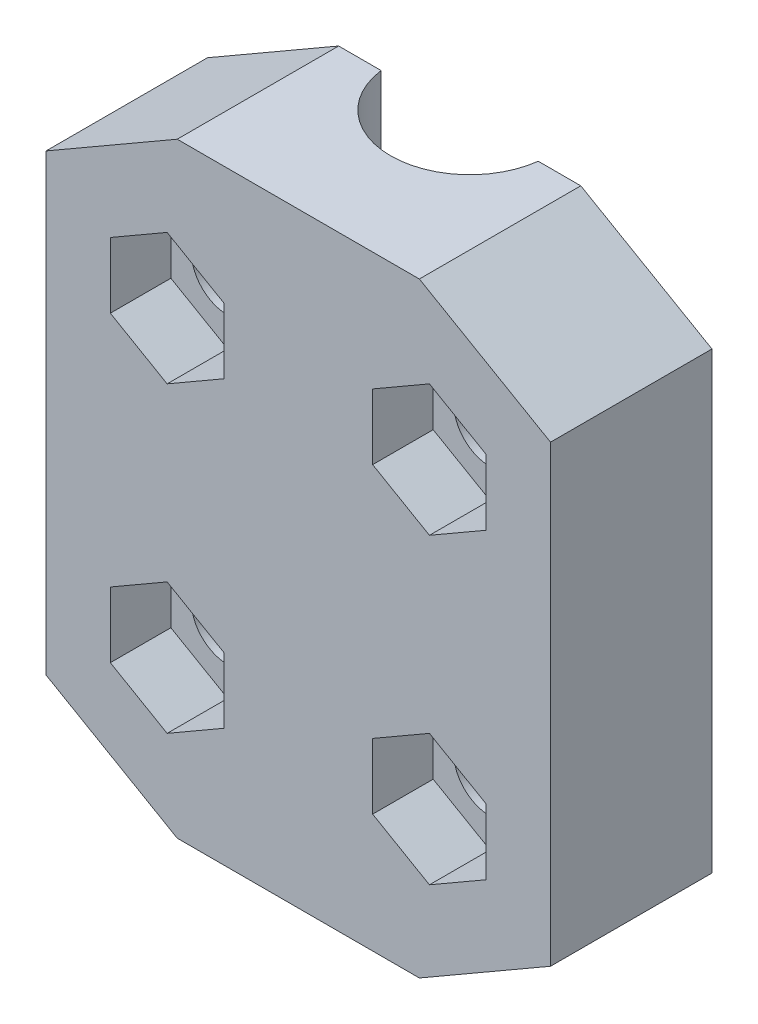
SolidWorks part; units mm, degrees
ref_plane "Piano frontale" through (0, 0, 0) normal (0, 0, 1) x (1, 0, 0)
ref_plane "Piano superiore" through (0, 0, 0) normal (0, 1, 0) x (1, 0, 0)
ref_plane "Piano destro" through (0, 0, 0) normal (1, 0, 0) x (0, 0, -1)
sketch "Schizzo1" plane through (0, 0, 0) normal (0, 0, 1) x (1, 0, 0)
  line L0 (0, -15) -> (0, 15) construction
  line L1 (0, 0) -> (12.5, 0) construction
  line L2 (12.5, -11.2472) -> (12.5, 11.2472)
  line L3 (-6, 15) -> (6, 15)
  line L4 (-12.5, 11.2472) -> (-6, 15)
  line L5 (-12.5, -11.2472) -> (-12.5, 11.2472)
  line L6 (12.5, -11.2472) -> (6, -15)
  line L7 (-12.5, -11.2472) -> (-6, -15)
  line L8 (12.5, 11.2472) -> (6, 15)
  line L9 (-6, -15) -> (6, -15)
  circle A0 centre (-6.5, 7.5) radius 1.8
  circle A1 centre (6.5, -7.5) radius 1.8
  circle A2 centre (-6.5, -7.5) radius 1.8
  circle A3 centre (6.5, 7.5) radius 1.8
  point P21 (-12.5, 0)
  dimension "D4" = 7.5
  dimension "D6" = 3.6
  dimension "D1" = 120
  dimension "D2" = 15
  dimension "D3" = 12.5
  dimension "D5" = 6
  dimension "D7" = 6
extrude "Main Body" add sketch "Schizzo1" along normal blind 8
sketch "Schizzo2" plane through (0, 15, 0) normal (0, 1, 0) x (1, 0, 0)
  line L0 (0, 0.5) -> (0, 0) construction
  line L1 (6, 0) -> (-6, 0) construction
  circle A0 centre (0, 0.5) radius 3.925
  dimension "D1" = 7.85
  dimension "D2" = 0.5
extrude "Threaded rod" cut sketch "Schizzo2" against normal blind 15
sketch "Schizzo4" plane through (0, -15, 0) normal (0, -1, 0) x (1, 0, 0)
  arc A0 (3.893, 0) -> (-3.893, 0) centre (0, -0.5) ccw construction
  arc A1 (3.893, 0) -> (-3.893, 0) centre (0, -0.5) ccw construction
  circle A2 centre (0, -0.5) radius 3.4325
  dimension "D1" = 6.865
extrude "Motor shaft" cut sketch "Schizzo4" against normal up to surface (15 mm away) up to face at (0, 0, 1.7125)
sketch "Schizzo5" plane through (0, 0, 8) normal (0, 0, 1) x (1, 0, 0)
  line L0 (0, 15) -> (0, -15) construction
  line L1 (6, 15) -> (-6, 15) construction
  line L2 (-6, -15) -> (6, -15) construction
  line L3 (-12.5, 0) -> (12.5, 0) construction
  line L4 (-12.5, 11.2472) -> (-12.5, -11.2472) construction
  line L5 (12.5, -11.2472) -> (12.5, 11.2472) construction
  line L6 (-9.3146, -5.875) -> (-6.5, -4.25)
  line L7 (6.5, -4.25) -> (3.6854, -5.875)
  line L8 (3.6854, -5.875) -> (3.6854, -9.125)
  line L9 (3.6854, -9.125) -> (6.5, -10.75)
  line L10 (6.5, -10.75) -> (9.3146, -9.125)
  line L11 (9.3146, -9.125) -> (9.3146, -5.875)
  line L12 (9.3146, -5.875) -> (6.5, -4.25)
  line L13 (-9.3146, -9.125) -> (-9.3146, -5.875)
  line L14 (-6.5, -10.75) -> (-9.3146, -9.125)
  line L15 (-3.6854, -9.125) -> (-6.5, -10.75)
  line L16 (-3.6854, -5.875) -> (-3.6854, -9.125)
  line L17 (-6.5, -4.25) -> (-3.6854, -5.875)
  line L18 (-6.5, 4.25) -> (-3.6854, 5.875)
  line L19 (-3.6854, 5.875) -> (-3.6854, 9.125)
  line L20 (-3.6854, 9.125) -> (-6.5, 10.75)
  line L21 (-6.5, 10.75) -> (-9.3146, 9.125)
  line L22 (-9.3146, 9.125) -> (-9.3146, 5.875)
  line L23 (9.3146, 5.875) -> (6.5, 4.25)
  line L24 (9.3146, 9.125) -> (9.3146, 5.875)
  line L25 (6.5, 10.75) -> (9.3146, 9.125)
  line L26 (3.6854, 9.125) -> (6.5, 10.75)
  line L27 (3.6854, 5.875) -> (3.6854, 9.125)
  line L28 (6.5, 4.25) -> (3.6854, 5.875)
  line L29 (-9.3146, 5.875) -> (-6.5, 4.25)
  circle A0 centre (6.5, -7.5) radius 1.8 construction
  circle A1 centre (6.5, -7.5) radius 1.8 construction
  circle A2 centre (6.5, -7.5) radius 2.8146 construction
  circle A3 centre (-6.5, -7.5) radius 2.8146 construction
  circle A4 centre (-6.5, -7.5) radius 1.8 construction
  circle A5 centre (-6.5, 7.5) radius 1.8 construction
  circle A6 centre (-6.5, 7.5) radius 2.8146 construction
  circle A7 centre (6.5, 7.5) radius 2.8146 construction
  circle A8 centre (6.5, 7.5) radius 1.8 construction
  dimension "D1" = 6.5
extrude "Nut recess" cut sketch "Schizzo5" against normal blind 3
ref_axis "Threaded rod axis" through (0, 0, -0.5) along (0, 1, 0)
ref_axis "Shaft" through (0, 0, -0.5) along (0, -1, 0)
ref_axis "Hole axis 1" through (6.5, -7.5, 5) along (0, 0, -1)
ref_axis "Hole axis 2" through (6.5, 7.5, 5) along (0, 0, -1)
ref_axis "Hole axis 3" through (-6.5, -7.5, 5) along (0, 0, -1)
ref_axis "Hole axis 4" through (-6.5, 7.5, 5) along (0, 0, -1)
